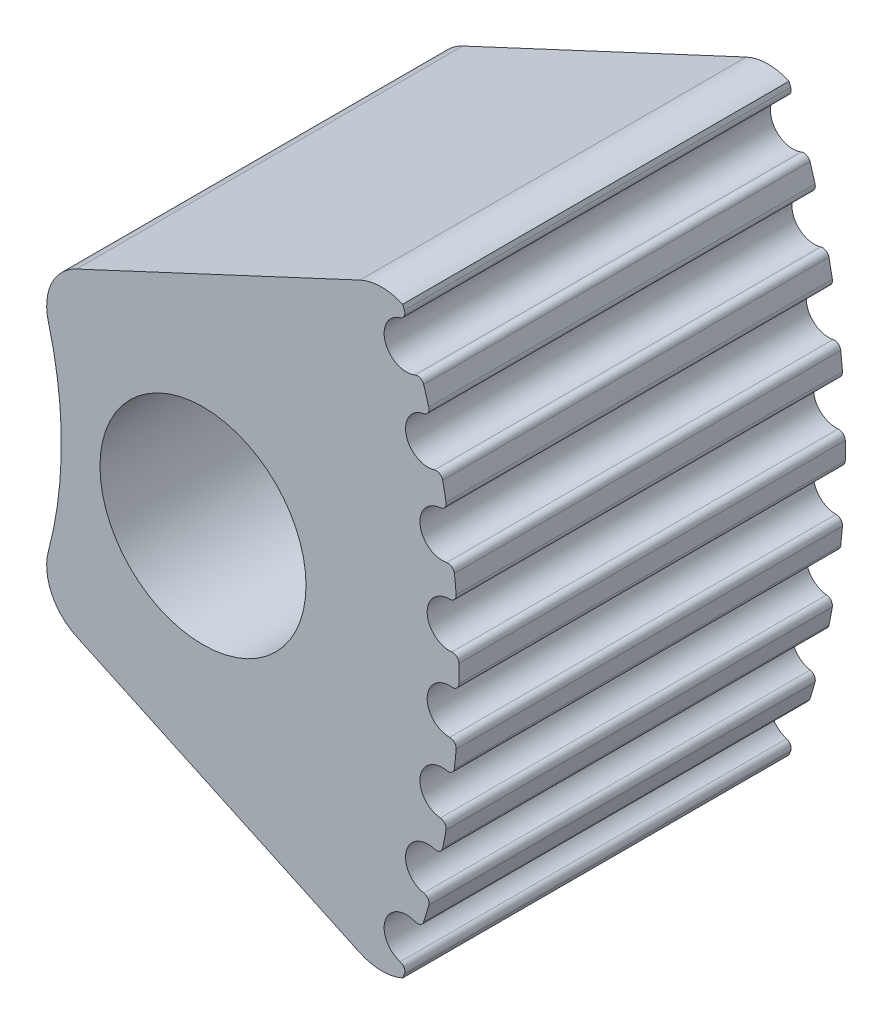
SolidWorks part; units mm, degrees
ref_plane "Front Plane" through (0, 0, 0) normal (0, 0, 1) x (1, 0, 0)
ref_plane "Top Plane" through (0, 0, 0) normal (0, 1, 0) x (1, 0, 0)
ref_plane "Right Plane" through (0, 0, 0) normal (1, 0, 0) x (0, 0, -1)
sketch "Sketch1" plane through (0, 0, 0) normal (0, 0, 1) x (1, 0, 0)
  line L0 (0, 0) -> (31.04, 0) construction
  line L1 (15.5848, 6.1776) -> (26.5969, 11.3126)
  line L2 (15.5848, -6.1776) -> (26.5969, -11.3126)
  arc A0 (14.4971, -3.8515) -> (14.4971, 3.8515) centre (0, 0) ccw
  arc A1 (29.3321, -10.1543) -> (29.3321, 10.1543) centre (0, 0) ccw
  arc A2 (26.5969, 11.3126) -> (29.3321, 10.1543) centre (27.4422, 9.5) cw
  arc A3 (15.5848, 6.1776) -> (14.4971, 3.8515) centre (16.4301, 4.365) ccw
  arc A4 (26.5969, -11.3126) -> (29.3321, -10.1543) centre (27.4422, -9.5) ccw
  arc A5 (15.5848, -6.1776) -> (14.4971, -3.8515) centre (16.4301, -4.365) cw
  dimension "D1" = 31.04
  dimension "D2" = 25
  dimension "D3" = 2
  dimension "D4" = 15
  dimension "D5" = 9.5
extrude "Corpo" add sketch "Sketch1" along normal blind 15
hole_wizard "Rebaixo - Parafuso M4" positions "Sketch5" profile "Sketch6" counterbore size "M4" standard "ANSI Metric"
sketch "Sketch5" plane through (0, 0, 15) normal (0, 0, 1) x (1, 0, 0)
  line L0 (15, 0) -> (31.04, 0) construction
  arc A0 (14.4971, -3.8515) -> (14.4971, 3.8515) centre (0, 0) ccw construction
  arc A1 (29.3321, -10.1543) -> (29.3321, 10.1543) centre (0, 0) ccw construction
  point P0 (20.5, 0)
  dimension "D1" = 5.5
sketch "Sketch6" plane through (20.5, 0, 15) normal (1, 0, 0) x (0, -1, 0)
  line L0 (0, 0) -> (0, 31.3519)
  line L1 (0, 31.3519) -> (2.25, 30)
  line L2 (2.25, 30) -> (2.25, 9)
  line L3 (2.25, 9) -> (4, 9)
  line L4 (4, 9) -> (4, 0)
  line L5 (4, 0) -> (0, 0)
  line L10 (0, 31.3519) -> (-2.25, 30) construction
  line L11 (0, -6.35) -> (0, 107.95) construction
  dimension "Hole Dia." = 4.5
  dimension "Hole Depth" = 30
  dimension "C'Bore Dia." = 8
  dimension "C'Bore Depth" = 9
  dimension "Drill Angle" = 118
sketch "Sketch7" plane through (0, 0, 15) normal (0, 0, 1) x (1, 0, 0)
  line L0 (0, 0) -> (30.44, 0) construction
  line L1 (0, 0) -> (31.0037, -1.5001) construction
  line L2 (30.44, 0) -> (31.04, 0)
  line L3 (30.2978, -2.9387) -> (30.895, -2.9966)
  arc A0 (31.04, 0) -> (30.895, -2.9966) centre (0, 0) cw
  arc A1 (30.44, 0) -> (30.4381, -0.3437) centre (0, 0) cw
  arc A2 (30.4381, -0.3437) -> (30.1628, -0.5896) centre (30.1881, -0.3409) cw
  arc A3 (30.1628, -0.5896) -> (30.0788, -2.3251) centre (30.0748, -1.4551) ccw
  arc A4 (29.3321, -10.1543) -> (29.3321, 10.1543) centre (0, 0) ccw construction
  arc A5 (30.3291, -2.5964) -> (30.0788, -2.3251) centre (30.08, -2.5751) ccw
  arc A6 (30.2978, -2.9387) -> (30.3291, -2.5964) centre (0, 0) ccw
  point P10 (30.0748, -1.4551)
  point P16 (31.0059, -1.4551)
  point P21 (31.0037, -1.5001)
  dimension "D1" = 0.87
  dimension "D2" = 0.25
  dimension "D4" = 1.8
  dimension "D3" = 0.6
  dimension "D5" = 2.77
extrude "Corte do Dente" cut sketch "Sketch7" against normal through all
pattern_circular "Corte dos Dentes" count 65 over 360 about axis through (0, 0, 15) along (0, 0, -1) of "Corte do Dente"
equation "\"n\"= 65'Number of Teeth"
equation "\"p\"= 3mm'Pitch"
equation "\"pd\"= \"n\" * \"p\" / pi'Pitch Diameter"
equation "\"D1@Corte dos Dentes\"=\"n\""
